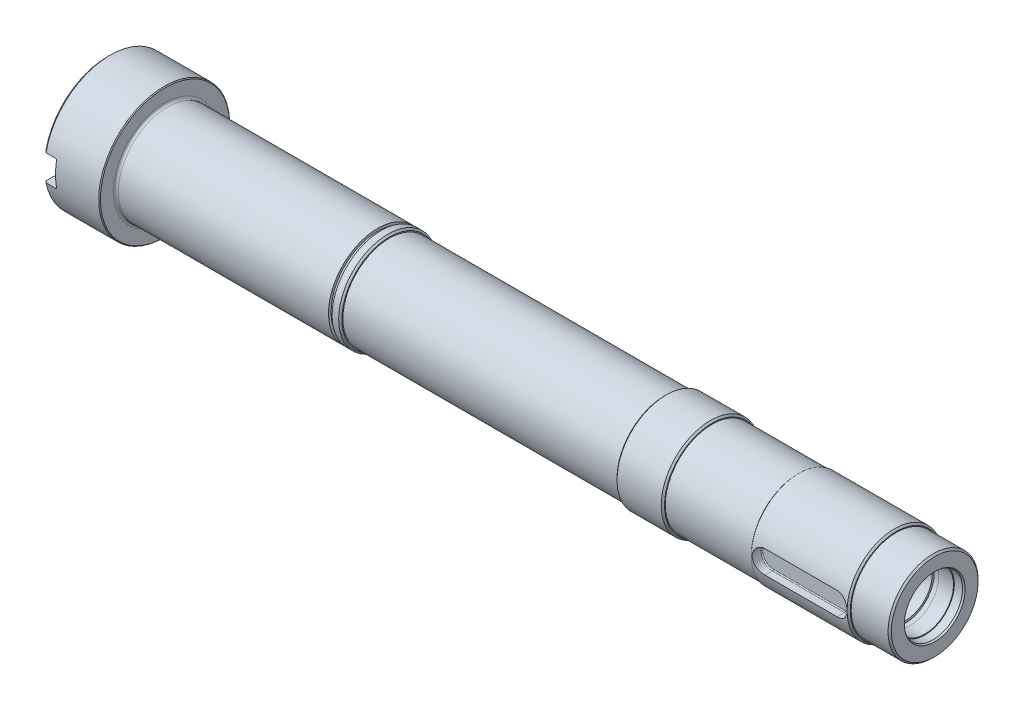
SolidWorks part; units mm, degrees
material "8620 STEEL"
ref_plane "Front Plane" through (0, 0, 0) normal (0, 0, 1) x (1, 0, 0)
ref_plane "Top Plane" through (0, 0, 0) normal (0, 1, 0) x (1, 0, 0)
ref_plane "Right Plane" through (0, 0, 0) normal (1, 0, 0) x (0, 0, -1)
sketch "Sketch1" plane through (0, 0, 0) normal (0, 0, 1) x (1, 0, 0)
  line L0 (-259.7519, 0) -> (1096.2574, 0) construction
  line L1 (0, 38.5) -> (0, 22.225)
  line L2 (1.5, 40) -> (35, 40)
  line L3 (172, 28.4) -> (340, 28.4)
  line L4 (172, 28.4) -> (172, 30)
  line L5 (164.8156, 30) -> (164.8156, 28.4353)
  line L6 (0, 22.225) -> (57.7709, 13.8)
  line L10 (164.8156, 28.4353) -> (167, 28.4353)
  line L11 (167, 28.4353) -> (167, 30)
  line L12 (167, 30) -> (172, 30)
  line L14 (340, 28.4) -> (340, 30)
  line L15 (340, 30) -> (369, 30)
  line L18 (487, 16.5) -> (487, 17.75)
  line L19 (170, 13.5) -> (170, 12.7)
  line L20 (487, 17.75) -> (490, 17.75)
  line L21 (1.5, 40) -> (0, 38.5)
  line L22 (35, 30) -> (164.8156, 30)
  line L23 (505, 27.5) -> (505, 18.5774)
  line L24 (490, 17.75) -> (490, 17.5)
  line L27 (170, 13.5) -> (117, 13.5)
  line L28 (57.7709, 13.8) -> (71.0668, 20)
  line L29 (71.0668, 20) -> (78.6962, 20)
  line L30 (78.6962, 20) -> (79.5, 17)
  line L31 (79.5, 17) -> (86.5, 17)
  line L32 (86.5, 17) -> (86.5, 17.25)
  line L33 (86.5, 17.25) -> (95.7327, 17.25)
  line L34 (95.7327, 17.25) -> (117, 13.5)
  line L35 (35, 30) -> (35, 40)
  line L36 (369, 30) -> (369, 28.5)
  line L37 (499, 17.5) -> (499, 18)
  line L38 (499, 18) -> (504, 18)
  line L39 (504, 18) -> (505, 18.5774)
  line L40 (170, 12.7) -> (278.5, 12.7)
  line L41 (278.5, 12.7) -> (278.5, 16)
  line L42 (278.5, 16) -> (285.5, 16)
  line L43 (285.5, 16) -> (285.5, 16.5)
  line L44 (285.5, 16.5) -> (487, 16.5)
  line L45 (490, 17.5) -> (499, 17.5)
  line L47 (369, 28.5) -> (421.5, 28.5)
  line L48 (421.5, 29) -> (421.5, 28.5)
  line L51 (481.5, 29) -> (481.5, 27.5)
  line L53 (421.5, 29) -> (481.5, 29)
  line L54 (481.5, 27.5) -> (505, 27.5)
  point P14 (167, 29.2177)
  point P64 (493.25, 27.5)
  dimension "D47" = 32
  dimension "D43" = 36
  dimension "D6" = 56.8
  dimension "D1" = 80
  dimension "D2" = 1.5
  dimension "D7" = 44.45
  dimension "D8" = 1.5
  dimension "D9" = 25
  dimension "D10" = 81.703
  dimension "D11" = 2.1844
  dimension "D12" = 340
  dimension "D13" = 60
  dimension "D14" = 40
  dimension "D15" = 132
  dimension "D16" = 5
  dimension "D17" = 56.8706
  dimension "D22" = 505
  dimension "D23" = 57
  dimension "D25" = 226.5
  dimension "D26" = 7
  dimension "D27" = 369
  dimension "D28" = 58
  dimension "D29" = 27
  dimension "D30" = 117
  dimension "D31" = 79.5
  dimension "D32" = 105
  dimension "D33" = 34
  dimension "D34" = 34.5
  dimension "D35" = 10
  dimension "D36" = 7
  dimension "D37" = 27.6
  dimension "D38" = 55
  dimension "D39" = 60
  dimension "D40" = 30
  dimension "D41" = 1
  dimension "D42" = 6
  dimension "D44" = 25.4
  dimension "D45" = 170
  dimension "D46" = 33
  dimension "D48" = 35.5
  dimension "D49" = 3
  dimension "D50" = 18
  dimension "D51" = 35
  dimension "D52" = 60
  dimension "D53" = 35
  dimension "D54" = 421.5
revolve "Revolve1" add sketch "Sketch1" angle 360 about L0
sketch "Sketch2" plane through (0, 0, 0) normal (0, 0, 1) x (1, 0, 0)
  line L0 (0, 38.5) -> (0, -38.5) construction
  line L1 (0, 7.9375) -> (8.1026, 7.9375)
  line L2 (0, 7.9375) -> (0, -7.9375)
  line L3 (0, -7.9375) -> (8.1026, -7.9375)
  line L4 (8.1026, 7.9375) -> (8.1026, -7.9375)
  dimension "D1" = 8.1026
  dimension "D2" = 15.875
  dimension "D3" = 7.9375
extrude "Cut-Extrude1" cut sketch "Sketch2" along normal through all
fillet "Fillet1" radius 0.9 2 edges at (8.1026, -7.9375, 29.3467) (8.1026, 7.9375, 29.3467)
chamfer "Chamfer1" distance 0.5 angle 45 2 edges at (0, -7.9375, 29.2161) (0, 7.9375, 29.2161)
chamfer "Chamfer2" distance 0.68 angle 45 1 edges at (0, 0, -22.225) first distance on face at (0, 0, -0.65)
hole_wizard "M6x1.0 Tapped Hole3" positions "Sketch4" profile "Sketch3" tap size "M6x1.0" standard "Ansi Metric"
sketch "Sketch4" plane through (8.1026, 0, 0) normal (-1, 0, 0) x (0, 0, 1)
  point P0 (33.15, 0)
  dimension "D1" = 33.15
sketch "Sketch3" plane through (8.1026, 0, 33.15) normal (0, 1, 0) x (0, 0, 1)
  line L0 (0, 0) -> (0, 16.4882)
  line L1 (0, 16.4882) -> (2.5, 14.986)
  line L2 (2.5, 14.986) -> (2.5, 0)
  line L5 (2.5, 0) -> (0, 0)
  line L10 (0, 16.4882) -> (-2.5, 14.986) construction
  line L11 (0, -6.35) -> (0, 107.95) construction
  dimension "Tap Drill Dia." = 5
  dimension "Tap Drill Depth" = 14.986
  dimension "Drill Angle" = 118
cosmetic thread "Hole Thread1" parameters "D1"=11.9888, "D2"=6
ref_plane "Plane1" through (0, 0, 23) normal (0, 0, 1) x (1, 0, 0)
sketch "Sketch5" plane through (0, 0, 23) normal (0, 0, 1) x (1, 0, 0)
  line L0 (429.5, 0) -> (473.5, 0) construction
  line L1 (429.5, 7) -> (473.5, 7)
  line L2 (429.5, -7) -> (473.5, -7)
  line L4 (0, 38.5) -> (0, -38.5) construction
  arc A0 (429.5, 7) -> (429.5, -7) centre (429.5, 0) ccw
  arc A1 (473.5, -7) -> (473.5, 7) centre (473.5, 0) ccw
  point P3 (451.5, 0)
  dimension "D3" = 429.5
  dimension "D1" = 14
  dimension "D2" = 44
extrude "Cut-Extrude2" cut sketch "Sketch5" along normal through all
fillet "Fillet9" radius 0.6 4 edges at (480.5, 0, 23) (451.5, 7, 23) (422.5, 0, 23) (451.5, -7, 23)
chamfer "Chamfer3" distance 1 angle 45 1 edges at (505, 0, 27.5)
fillet "Fillet11" radius 1.5 1 edges at (35, 0, 30)
chamfer "Chamfer4" distance 0.5 angle 45 1 edges at (35, 0, 40)
chamfer "Chamfer5" distance 1 angle 45 1 edges at (172, 0, 30)
chamfer "Chamfer6" distance 1 angle 45 2 edges at (340, 0, 30) (369, 0, 30)
chamfer "Chamfer8" distance 1 angle 45 1 edges at (481.5, 0, 29)
chamfer "Chamfer9" distance 0.5 angle 45 1 edges at (421.5, 0, 29)
equation "\"D3@Sketch2\" = \"D2@Sketch2\"/2"
